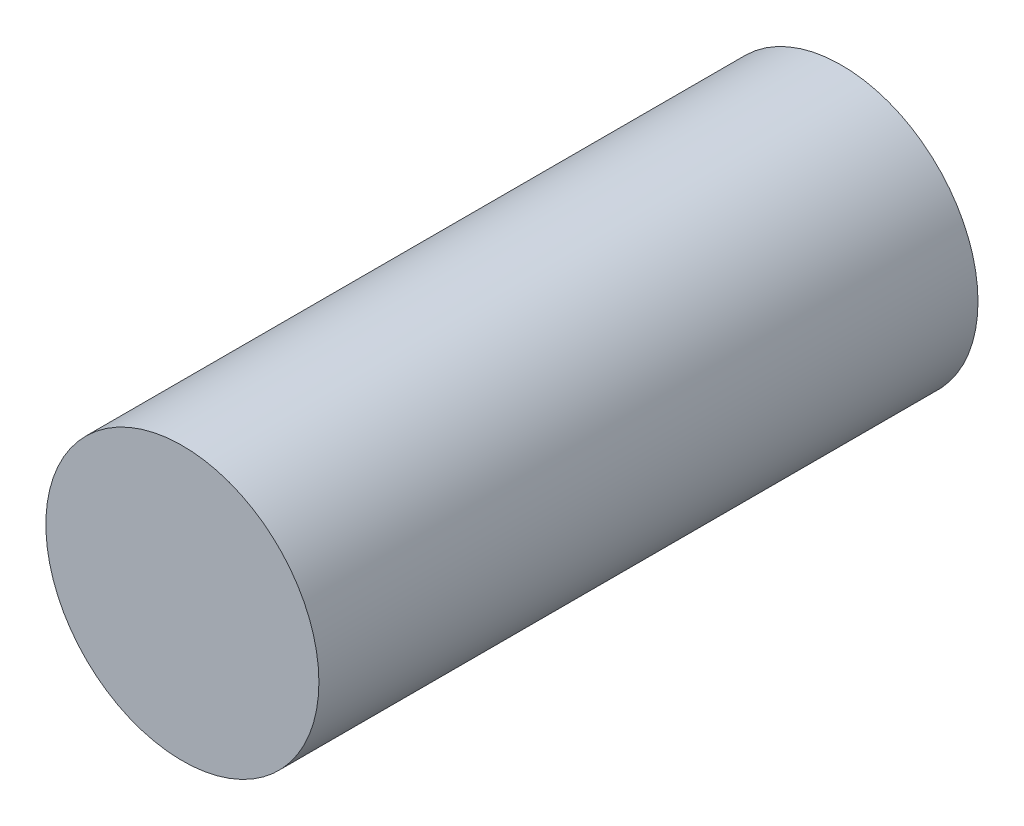
SolidWorks part; units mm, degrees
ref_plane "Front Plane" through (0, 0, 0) normal (0, 0, 1) x (1, 0, 0)
ref_plane "Top Plane" through (0, 0, 0) normal (0, 1, 0) x (1, 0, 0)
ref_plane "Right Plane" through (0, 0, 0) normal (1, 0, 0) x (0, 0, -1)
sketch "Sketch1" plane through (0, 0, 0) normal (0, 0, 1) x (1, 0, 0)
  circle A0 centre (0, 0) radius 36.83
  dimension "D1" = 73.66
extrude "Boss-Extrude1" add sketch "Sketch1" along normal blind 177.8
ref_axis "Axis1" through (0, 0, -7.62) along (0, 0, 1)
